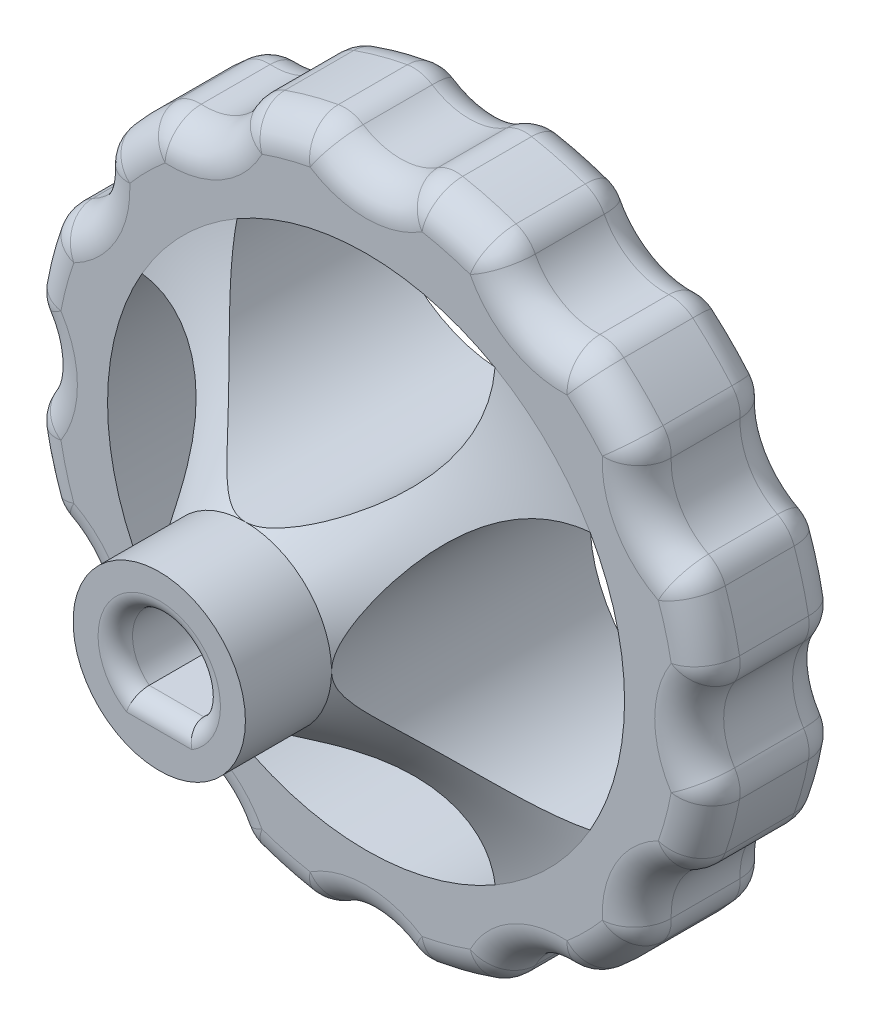
SolidWorks part; units mm, degrees
ref_plane "Front" through (0, 0, 0) normal (0, 0, 1) x (1, 0, 0)
ref_plane "Top" through (0, 0, 0) normal (0, 1, 0) x (1, 0, 0)
ref_plane "Right" through (0, 0, 0) normal (1, 0, 0) x (0, 0, -1)
other "Graphic1"
sketch "Sketch1" plane through (0, 0, 0) normal (1, 0, 0) x (0, 0, -1)
  line L0 (0, 0) -> (20, 0) construction
  line L1 (0, 0) -> (0, 5)
  line L2 (0, 5) -> (5, 5)
  line L3 (20, 0) -> (20, 20)
  line L4 (20, 20) -> (12, 20)
  line L5 (12, 20) -> (12, 15)
  line L6 (0, 0) -> (20, 0)
  arc A0 (12, 15) -> (5, 5) centre (-2.7253, 17.8577) cw
  point P9 (12, 13.8236)
  dimension "D3" = 8
  dimension "D6" = 15
  dimension "D1" = 5
  dimension "D2" = 10
  dimension "D4" = 20
  dimension "D5" = 40
  dimension "D7" = 5
revolve "Revolve3" add sketch "Sketch1" angle 360 about L0
sketch "Sketch5" plane through (0, 0, -20) normal (0, 0, -1) x (-1, 0, 0)
  arc A2 (7.4833, 13) -> (-7.4833, 13) centre (0, 0) ccw
  circle A3 centre (0, 0) radius 15 construction
  arc A4 (-7.4833, 13) -> (7.4833, 13) centre (0, 12.5) ccw
  circle A5 centre (0, 0) radius 5 construction
  point P11 (0, 0)
  point P12 (0, 0)
  dimension "D1" = 7.5
extrude "Cut-Extrude1" cut sketch "Sketch5" against normal through all
pattern_circular "CirPattern1" count 4 over 360 about axis through (0, 0, 0) along (0, 0, 1) of "Cut-Extrude1"
sketch "Sketch6" plane through (0, 0, 0) normal (0, 0, 1) x (1, 0, 0)
  line L0 (1.5819, -2) -> (-1.5819, -2)
  arc A3 (1.5819, -2) -> (-1.5819, -2) centre (0, 0) ccw
  dimension "D3" = 5.1
  dimension "D4" = 2
extrude "Cut-Extrude3" cut sketch "Sketch6" against normal blind 10
sketch "Sketch7" plane through (0, 0, -20) normal (0, 0, -1) x (-1, 0, 0)
  circle A0 centre (0, -22.75) radius 4
  point P2 (0, 0)
  point P4 (0, -23.4859)
  point P5 (0, -22.7306)
  dimension "D1" = 8
  dimension "D2" = 22.75
extrude "Cut-Extrude2" cut sketch "Sketch7" against normal through all
pattern_circular "CirPattern2" count 12 over 360 about axis through (0, 0, 0) along (0, 0, 1) of "Cut-Extrude2"
fillet "Fillet1" radius 2 24 edges at (-2.7172, -19.8146, -16) (2.7172, -19.8146, -16) (7.5541, -18.5185, -16) (12.2604, -15.8013, -16) (15.8013, -12.2604, -16) (18.5185, -7.5541, -16) (19.8146, -2.7172, -16) (19.8146, 2.7172, -16) (18.5185, 7.5541, -16) (15.8013, 12.2604, -16) (12.2604, 15.8013, -16) (7.5541, 18.5185, -16) (2.7172, 19.8146, -16) (-2.7172, 19.8146, -16) (-7.5541, 18.5185, -16) (-12.2604, 15.8013, -16) (-15.8013, 12.2604, -16) (-18.5185, 7.5541, -16) (-19.8146, 2.7172, -16) (-19.8146, -2.7172, -16) (-18.5185, -7.5541, -16) (-15.8013, -12.2604, -16) (-12.2604, -15.8013, -16) (-7.5541, -18.5185, -16)
fillet "Fillet2" radius 2 96 edges at (-19.6667, 2.8593, -12) (-19.3185, 5.1764, -12) (-18.4615, 7.3572, -12) (-16.238, 9.375, -12) (-15.6022, 12.3095, -12) (-14.1421, 14.1421, -12) (-12.3095, 15.6022, -12) (-9.375, 16.238, -12) (-7.3572, 18.4615, -12) (-5.1764, 19.3185, -12) (-2.8593, 19.6667, -12) (0, 18.75, -12) (2.8593, 19.6667, -12) (5.1764, 19.3185, -12) (7.3572, 18.4615, -12) (9.375, 16.238, -12) (12.3095, 15.6022, -12) (14.1421, 14.1421, -12) (15.6022, 12.3095, -12) (16.238, 9.375, -12) (18.4615, 7.3572, -12) (19.3185, 5.1764, -12) (19.6667, 2.8593, -12) (18.75, 0, -12) (19.6667, -2.8593, -12) (19.3185, -5.1764, -12) (18.4615, -7.3572, -12) (16.238, -9.375, -12) (15.6022, -12.3095, -12) (14.1421, -14.1421, -12) (12.3095, -15.6022, -12) (9.375, -16.238, -12) (7.3572, -18.4615, -12) (5.1764, -19.3185, -12) (2.8593, -19.6667, -12) (0, -18.75, -12) (-2.8593, -19.6667, -12) (-5.1764, -19.3185, -12) (-7.3572, -18.4615, -12) (-9.375, -16.238, -12) (-12.3095, -15.6022, -12) (-14.1421, -14.1421, -12) (-15.6022, -12.3095, -12) (-16.238, -9.375, -12) (-18.4615, -7.3572, -12) (-19.3185, -5.1764, -12) (-19.6667, -2.8593, -12) (-19.6667, 2.8593, -20) (-19.3185, 5.1764, -20) (-18.4615, 7.3572, -20) (-16.238, 9.375, -20) (-15.6022, 12.3095, -20) (-14.1421, 14.1421, -20) (-12.3095, 15.6022, -20) (-9.375, 16.238, -20) (-7.3572, 18.4615, -20) (-5.1764, 19.3185, -20) (-2.8593, 19.6667, -20) (0, 18.75, -20) (2.8593, 19.6667, -20) (5.1764, 19.3185, -20) (7.3572, 18.4615, -20) (9.375, 16.238, -20) (12.3095, 15.6022, -20) (14.1421, 14.1421, -20) (15.6022, 12.3095, -20) (16.238, 9.375, -20) (18.4615, 7.3572, -20) (19.3185, 5.1764, -20) (19.6667, 2.8593, -20) (18.75, 0, -20) (19.6667, -2.8593, -20) (19.3185, -5.1764, -20) (18.4615, -7.3572, -20) (16.238, -9.375, -20) (15.6022, -12.3095, -20) (14.1421, -14.1421, -20) (12.3095, -15.6022, -20) (9.375, -16.238, -20) (7.3572, -18.4615, -20) (5.1764, -19.3185, -20) (2.8593, -19.6667, -20) (0, -18.75, -20) (-2.8593, -19.6667, -20) (-5.1764, -19.3185, -20) (-7.3572, -18.4615, -20) (-9.375, -16.238, -20) (-12.3095, -15.6022, -20) (-14.1421, -14.1421, -20) (-15.6022, -12.3095, -20) (-16.238, -9.375, -20) (-18.4615, -7.3572, -20) (-19.3185, -5.1764, -20) (-19.6667, -2.8593, -20) (-18.75, 0, -12) (-18.75, 0, -20)
fillet "Fillet3" radius 1 2 edges at (0, 2.55, 0) (0, -2, 0)
